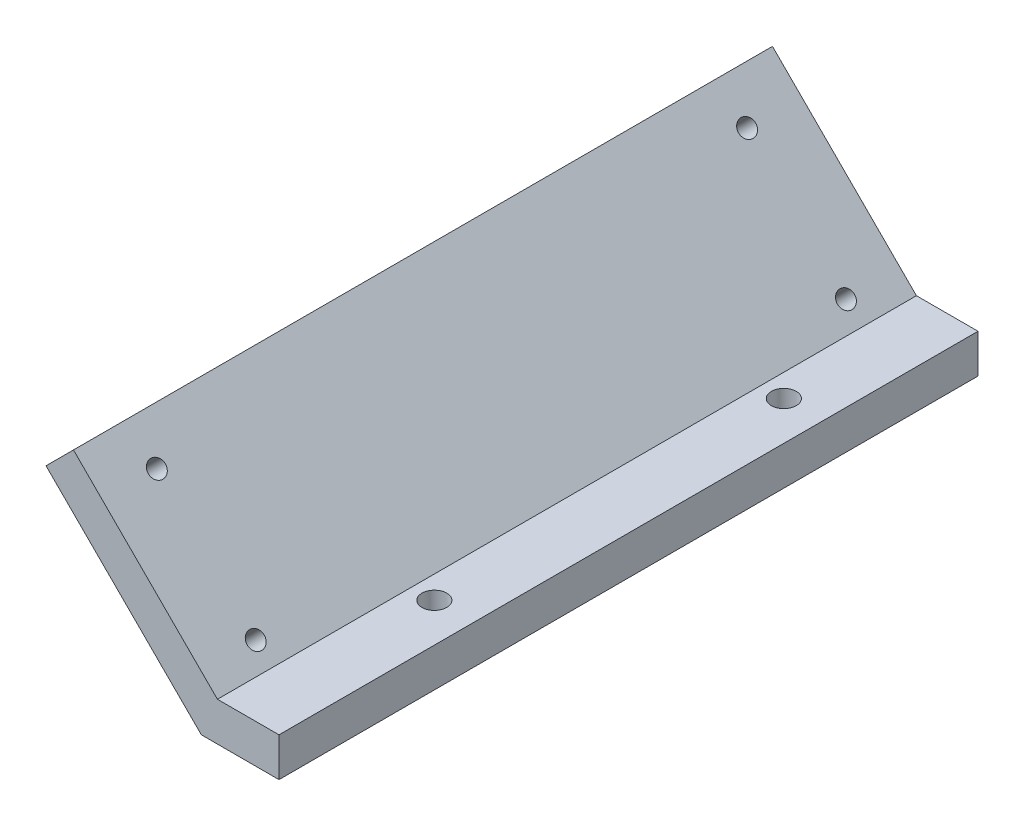
SolidWorks part; units mm, degrees
ref_plane "前视基准面" through (0, 0, 0) normal (0, 0, 1) x (1, 0, 0)
ref_plane "上视基准面" through (0, 0, 0) normal (0, 1, 0) x (1, 0, 0)
ref_plane "右视基准面" through (0, 0, 0) normal (1, 0, 0) x (0, 0, -1)
sketch "草图1" plane through (0, 0, 0) normal (0, 0, 1) x (1, 0, 0)
  line L0 (0, 0) -> (-20, 20)
  line L1 (0, 0) -> (10, 0)
  line L2 (2.0711, 5) -> (-16.4645, 23.5355)
  line L3 (2.0711, 5) -> (10, 5)
  line L4 (10, 5) -> (10, 0)
  line L5 (-16.4645, 23.5355) -> (-20, 20)
  dimension "D1" = 5
extrude "凸台-拉伸1" add sketch "草图1" along normal blind 90
sketch "草图2" plane through (0, 5, 0) normal (0, 1, 0) x (1, 0, 0)
  circle A3 centre (5, -20) radius 1.6
  circle A4 centre (5, -65) radius 1.6
extrude "切除-拉伸1" cut sketch "草图2" against normal blind 10
sketch "草图3" plane through (0, 0, 0) normal (-0.7071, -0.7071, 0) x (0, 0, 1)
  circle A0 centre (7, 23) radius 1.1
  circle A1 centre (83, 23) radius 1.1
  circle A2 centre (83, 5) radius 1.1
  circle A3 centre (7, 5) radius 1.1
  point P2 (0, 0)
  dimension "D1" = 2
  dimension "D2" = 2
extrude "切除-拉伸2" cut sketch "草图3" against normal blind 10
